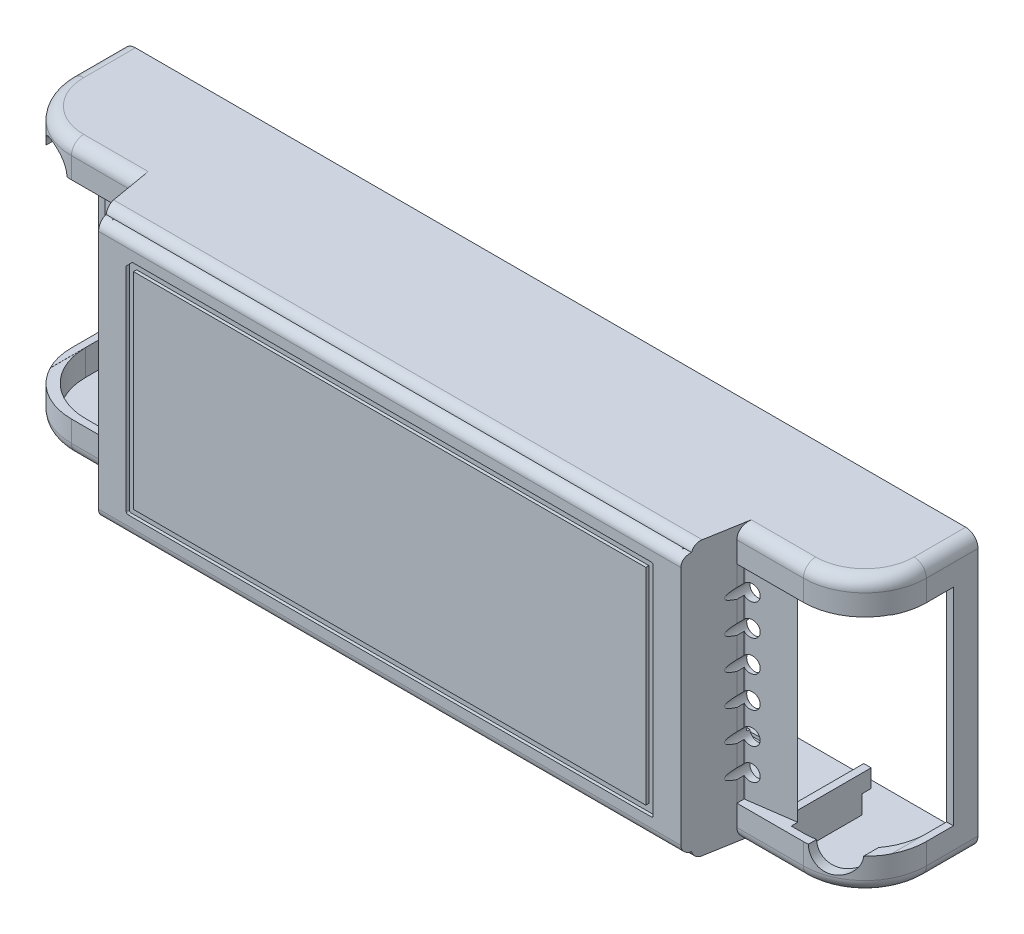
SolidWorks part; units mm, degrees
ref_plane "Front Plane" through (0, 0, 0) normal (0, 0, 1) x (1, 0, 0)
ref_plane "Top Plane" through (0, 0, 0) normal (0, 1, 0) x (1, 0, 0)
ref_plane "Right Plane" through (0, 0, 0) normal (1, 0, 0) x (0, 0, -1)
sketch "Sketch1" plane through (0, 0, 0) normal (0, 0, 1) x (1, 0, 0)
  line L1 (-34.7725, 22.265) -> (34.7725, 22.265)
  line L2 (-34.7725, 22.265) -> (-34.7725, -22.265)
  line L3 (-34.7725, -22.265) -> (34.7725, -22.265)
  line L4 (34.7725, 22.265) -> (34.7725, -22.265)
  line L5 (-34.7725, 22.265) -> (34.7725, -22.265) construction
  line L6 (-34.7725, -22.265) -> (34.7725, 22.265) construction
  point P0 (0, 0)
  dimension "D1" = 44.53
  dimension "D2" = 69.545
extrude "Boss-Extrude1" add sketch "Sketch1" along normal blind 26.17
sketch "Sketch2" plane through (0, 0, 26.17) normal (0, 0, 1) x (1, 0, 0)
  line L0 (-34.7725, -22.265) -> (34.7725, -22.265) construction
  line L1 (34.7725, 22.265) -> (13.9425, 22.265)
  line L2 (34.7725, 22.265) -> (34.7725, -22.265)
  line L3 (34.7725, -22.265) -> (13.9425, -22.265)
  line L4 (13.9425, 22.265) -> (13.9425, -22.265)
  dimension "D1" = 20.83
extrude "Cut-Extrude1" cut sketch "Sketch2" against normal blind 7.77
sketch "Sketch3" plane through (0, -22.265, 0) normal (0, -1, 0) x (1, 0, 0)
  line L0 (13.9425, 18.4) -> (13.9425, 26.17)
  line L1 (13.9425, 26.17) -> (12.5925, 26.17)
  line L2 (-34.7725, 26.17) -> (13.9425, 26.17) construction
  line L3 (12.5925, 26.17) -> (13.9425, 18.4)
  dimension "D1" = 22.18
extrude "Cut-Extrude2" cut sketch "Sketch3" against normal through all
sketch "Sketch4" plane through (0, 0, 18.4) normal (0, 0, 1) x (1, 0, 0)
  line L0 (13.9425, 22.265) -> (13.9425, -22.265) construction
  line L1 (63.8796, 16.865) -> (13.9425, 16.865)
  line L2 (63.8796, 16.865) -> (63.8796, -16.835)
  line L3 (63.8796, -16.835) -> (13.9425, -16.835)
  line L4 (13.9425, 16.865) -> (13.9425, -16.835)
  line L5 (34.7725, 22.265) -> (13.9425, 22.265) construction
  dimension "D1" = 33.7
  dimension "D2" = 0
  dimension "D3" = 5.4
extrude "Cut-Extrude3" cut sketch "Sketch4" against normal blind 1.2
sketch "Sketch5" plane through (0, 0, 18.4) normal (0, 0, 1) x (1, 0, 0)
  line L0 (13.9425, -16.835) -> (34.7725, -16.835) construction
  line L1 (33.6725, 16.865) -> (21.5925, 16.865)
  line L2 (33.6725, 16.865) -> (33.6725, -16.835)
  line L3 (33.6725, -16.835) -> (21.5925, -16.835)
  line L4 (21.5925, 16.865) -> (21.5925, -16.835)
  line L5 (34.7725, -22.265) -> (34.7725, -16.835) construction
  dimension "D1" = 33.7
  dimension "D2" = 12.08
  dimension "D3" = 1.1
extrude "Cut-Extrude4" cut sketch "Sketch5" against normal through all
sketch "Sketch6" plane through (34.7725, 0, 0) normal (1, 0, 0) x (0, 0, -1)
  line L0 (0, -22.265) -> (0, 22.265) construction
  line L1 (-10.22, -16.815) -> (-4, -16.815)
  line L2 (-10.22, -16.815) -> (-10.22, 16.815)
  line L3 (-10.22, 16.815) -> (-4, 16.815)
  line L4 (-4, -16.815) -> (-4, 16.815)
  line L5 (-18.4, 22.265) -> (0, 22.265) construction
  line L6 (-18.4, -22.265) -> (0, -22.265) construction
  dimension "D1" = 4
  dimension "D2" = 6.22
  dimension "D3" = 5.45
  dimension "D4" = 5.45
extrude "Cut-Extrude5" cut sketch "Sketch6" against normal blind 1.2
sketch "Sketch8" plane through (34.7725, 0, 0) normal (1, 0, 0) x (0, 0, -1)
  line L0 (-18.4, -22.265) -> (-18.4, -16.835) construction
  line L1 (-10.22, -16.815) -> (-18.4, -16.815)
  line L2 (-10.22, -16.815) -> (-10.22, 16.815)
  line L3 (-10.22, 16.815) -> (-18.4, 16.815)
  line L4 (-18.4, -16.815) -> (-18.4, 16.815)
extrude "Cut-Extrude6" cut sketch "Sketch8" against normal blind 1.2
sketch "Sketch9" plane through (21.5925, 0, 0) normal (1, 0, 0) x (0, 0, -1)
  line L0 (0, 16.865) -> (-17.2, 16.865) construction
  line L1 (0, -16.835) -> (-4.2, -16.835)
  line L2 (0, -16.835) -> (0, 16.865)
  line L3 (0, 16.865) -> (-4.2, 16.865)
  line L4 (-4.2, -16.835) -> (-4.2, 16.865)
  dimension "D1" = 4.2
extrude "Cut-Extrude7" cut sketch "Sketch9" against normal blind 5
sketch "Sketch11" plane through (21.5925, 0, 0) normal (1, 0, 0) x (0, 0, -1)
  line L0 (-4.2, 16.865) -> (-4.2, -16.835) construction
  line L1 (-16, -7.785) -> (-4.2, -7.785)
  line L2 (-16, -7.785) -> (-16, 7.815)
  line L3 (-16, 7.815) -> (-4.2, 7.815)
  line L4 (-4.2, -7.785) -> (-4.2, 7.815)
  line L5 (-17.2, -16.835) -> (-17.2, 16.865) construction
  line L6 (-4.2, -16.835) -> (-17.2, -16.835) construction
  dimension "D1" = 15.6
  dimension "D2" = 1.2
  dimension "D3" = 9.05
extrude "Cut-Extrude8" cut sketch "Sketch11" against normal blind 5
sketch "Sketch13" plane through (0, 16.865, 0) normal (0, -1, 0) x (1, 0, 0)
  line L0 (33.6725, 17.2) -> (21.5925, 17.2)
  line L1 (21.5925, 4.2) -> (21.5925, 17.2) construction
  line L2 (21.5925, 17.2) -> (21.5925, 4.2)
  line L3 (21.5925, 4.2) -> (16.5925, 4.2)
  line L4 (16.5925, 0) -> (16.5925, 4.2) construction
  line L5 (16.5925, 4.2) -> (21.5925, 4.2) construction
  line L6 (16.5925, 4.2) -> (16.5925, 0)
  line L7 (16.5925, 0) -> (33.6725, 0)
  line L8 (33.6725, 0) -> (33.6725, 17.2)
extrude "Cut-Extrude9" cut sketch "Sketch13" against normal blind 4.2
sketch "Sketch14" plane through (0, -16.835, 0) normal (0, 1, 0) x (1, 0, 0)
  line L0 (33.6725, -17.2) -> (21.5925, -17.2)
  line L1 (21.5925, -17.2) -> (21.5925, -4.2)
  line L2 (21.5925, -4.2) -> (16.5925, -4.2)
  line L3 (16.5925, -4.2) -> (16.5925, 0)
  line L4 (16.5925, 0) -> (33.6725, 0)
  line L5 (33.6725, 0) -> (33.6725, -17.2)
extrude "Cut-Extrude10" cut sketch "Sketch14" against normal blind 4.2
shell "Shell3" thickness 1.2
sketch "Sketch15" plane through (-34.7725, 0, 0) normal (-1, 0, 0) x (0, 0, 1)
  line L0 (26.17, 22.265) -> (0, 22.265) construction
  line L1 (24.97, 21.065) -> (0, 21.065)
  line L2 (24.97, 21.065) -> (24.97, -21.065)
  line L3 (24.97, -21.065) -> (0, -21.065)
  line L4 (0, 21.065) -> (0, -21.065)
  line L5 (26.17, 22.265) -> (26.17, -22.265) construction
  dimension "D1" = 1.2
  dimension "D2" = 1.2
extrude "Cut-Extrude11" cut sketch "Sketch15" against normal blind 4.2
sketch "Sketch16" plane through (16.5925, 0, 0) normal (1, 0, 0) x (0, 0, -1)
  line L0 (-16, -7.785) -> (-4.2, -7.785)
  line L1 (-4.2, -7.785) -> (-4.2, -21.035)
  line L2 (-4.2, -21.035) -> (0, -21.035)
  line L3 (0, -21.035) -> (0, 21.065)
  line L4 (0, 21.065) -> (-4.2, 21.065)
  line L5 (-4.2, 21.065) -> (-4.2, 7.815)
  line L6 (-4.2, 7.815) -> (-16, 7.815)
  line L7 (-16, 7.815) -> (-16, -7.785)
extrude "Cut-Extrude12" cut sketch "Sketch16" against normal blind 4.2
sketch "Sketch18" plane through (0, 0, 4.2) normal (0, 0, -1) x (-1, 0, 0)
  line L0 (-21.5925, 21.065) -> (-15.3925, 21.065) construction
  line L1 (-20.3925, 21.065) -> (-15.3925, 21.065)
  line L2 (-20.3925, 21.065) -> (-20.3925, 9.015)
  line L3 (-20.3925, 9.015) -> (-15.3925, 9.015)
  line L4 (-15.3925, 21.065) -> (-15.3925, 9.015)
  line L5 (-15.3925, 21.065) -> (-15.3925, 7.815) construction
  line L6 (-33.6725, -21.035) -> (-15.3925, -21.035) construction
  line L7 (-20.3925, -21.035) -> (-15.3925, -21.035)
  line L8 (-20.3925, -21.035) -> (-20.3925, -8.985)
  line L9 (-20.3925, -8.985) -> (-15.3925, -8.985)
  line L10 (-15.3925, -21.035) -> (-15.3925, -8.985)
  line L11 (-15.3925, -7.785) -> (-15.3925, -21.035) construction
  line L12 (-15.3925, -7.785) -> (-21.5925, -7.785) construction
  line L13 (-15.3925, 7.815) -> (-21.5925, 7.815) construction
  line L14 (-21.5925, -7.785) -> (-21.5925, -21.035) construction
  line L15 (-21.5925, 21.065) -> (-21.5925, 16.865) construction
  dimension "D1" = 1.2
  dimension "D2" = 1.2
  dimension "D3" = 1.2
  dimension "D4" = 1.2
extrude "Cut-Extrude13" cut sketch "Sketch18" against normal blind 4.2
sketch "Sketch19" plane through (0, 0, 24.97) normal (0, 0, -1) x (-1, 0, 0)
  line L0 (-11.583, 21.065) -> (-11.583, -21.065) construction
  line L1 (34.7725, -21.065) -> (-11.583, -21.065)
  line L2 (34.7725, -21.065) -> (34.7725, -19.565)
  line L3 (34.7725, -19.565) -> (-11.583, -19.565)
  line L4 (-11.583, -21.065) -> (-11.583, -19.565)
  line L5 (34.7725, -21.065) -> (34.7725, 21.065) construction
  line L6 (-11.583, 21.065) -> (34.7725, 21.065)
  line L7 (-11.583, 21.065) -> (-11.583, 19.565)
  line L8 (-11.583, 19.565) -> (34.7725, 19.565)
  line L9 (34.7725, 21.065) -> (34.7725, 19.565)
  dimension "D1" = 1.5
  dimension "D2" = 1.5
extrude "Boss-Extrude2" add sketch "Sketch19" along normal blind 2.5
sketch "Sketch22" plane through (0, 0, 26.17) normal (0, 0, 1) x (1, 0, 0)
  line L1 (12.5925, -22.265) -> (-37.0858, -22.265)
  line L2 (12.5925, -22.265) -> (12.5925, -21.065)
  line L3 (12.5925, -21.065) -> (-37.0858, -21.065)
  line L4 (-37.0858, -22.265) -> (-37.0858, -21.065)
  dimension "D1" = 1.2
extrude "Cut-Extrude16" cut sketch "Sketch22" against normal blind 1.5
sketch "Sketch23" plane through (12.5925, 0, 0) normal (-1, 0, 0) x (0, 0, 1)
  line L1 (24.67, -21.065) -> (26.17, -21.065)
  line L2 (24.67, -21.065) -> (24.67, -22.265)
  line L3 (24.67, -22.265) -> (26.17, -22.265)
  line L4 (26.17, -21.065) -> (26.17, -22.265)
extrude "Cut-Extrude17" cut sketch "Sketch23" against normal blind 1.5
sketch "Sketch24" plane through (0, 0, 26.17) normal (0, 0, 1) x (1, 0, 0)
  line L0 (12.5925, 22.265) -> (12.5925, -21.065) construction
  line L1 (-34.7725, 22.265) -> (12.5925, 22.265)
  line L2 (-34.7725, 22.265) -> (-34.7725, 21.065)
  line L3 (-34.7725, 21.065) -> (12.5925, 21.065)
  line L4 (12.5925, 22.265) -> (12.5925, 21.065)
  dimension "D1" = 1.2
extrude "Cut-Extrude18" cut sketch "Sketch24" against normal blind 1.5
sketch "Sketch25" plane through (12.5925, 0, 0) normal (-1, 0, 0) x (0, 0, 1)
  line L1 (24.67, 22.265) -> (26.17, 22.265)
  line L2 (24.67, 22.265) -> (24.67, 21.065)
  line L3 (24.67, 21.065) -> (26.17, 21.065)
  line L4 (26.17, 22.265) -> (26.17, 21.065)
extrude "Cut-Extrude19" cut sketch "Sketch25" against normal blind 1.5
sketch "Sketch26" plane through (0, 0, 26.17) normal (0, 0, 1) x (1, 0, 0)
  line L0 (-34.7725, 21.065) -> (11.583, 21.065) construction
  line L1 (8.0925, 17.9519) -> (-34.7725, 17.9519)
  line L2 (8.0925, 17.9519) -> (8.0925, -17.955)
  line L3 (8.0925, -17.955) -> (-34.7725, -17.955)
  line L4 (-34.7725, 17.9519) -> (-34.7725, -17.955)
  line L5 (12.5925, 21.065) -> (12.5925, -21.065) construction
  line L6 (-34.7725, 21.065) -> (-34.7725, -21.065) construction
  line L7 (12.5925, -21.065) -> (-34.7725, -21.065) construction
  line L9 (-34.7725, 16.7519) -> (6.8925, 16.7519)
  line L10 (-34.7725, 16.7519) -> (-34.7725, -16.755)
  line L11 (-34.7725, -16.755) -> (6.8925, -16.755)
  line L12 (6.8925, 16.7519) -> (6.8925, -16.755)
  line M9 (-34.7725, 21.065) -> (-34.7725, -21.065)
  dimension "D1" = 3.1131
  dimension "D2" = 4.5
  dimension "D3" = 0
  dimension "D4" = 3.11
  dimension "D5" = 1.2
  dimension "D6" = 1.2
  dimension "D7" = 1.2
extrude "Cut-Extrude20" cut sketch "Sketch26" against normal blind 0.5 contours L9 L12 L11 L3 L2 L1 M9
fillet "Fillet1" radius 1.5 4 edges at (-11.09, 21.065, 26.17) (-10.9597, 22.265, 24.67) (-11.09, -21.065, 26.17) (-10.9597, -22.265, 24.67)
fillet "Fillet5" radius 10 2 edges at (33.6725, 18.965, 17.2) (33.6725, -18.935, 17.2)
fillet "Fillet6" radius 10 2 edges at (34.7725, -19.55, 18.4) (34.7725, 19.565, 18.4)
fillet "Fillet7" radius 2 6 edges at (19.3575, 22.265, 18.4) (31.8436, 22.265, 15.4711) (19.3575, -22.265, 18.4) (31.8436, -22.265, 15.4711) (34.7725, 22.265, 4.2) (34.7725, -22.265, 4.2)
mirror "Mirror1" about plane through (-34.7725, 22.265, 26.17) normal (1, 0, 0) of bodies 122
sketch "Sketch27" plane through (0, 0, 4.2) normal (0, 0, -1) x (-1, 0, 0)
  line L1 (89.9375, 9.015) -> (84.9375, 9.015) construction
  line L2 (84.9375, 7.815) -> (87.8509, 7.815)
  line L3 (84.9375, 7.815) -> (84.9375, 9.015)
  line L4 (84.9375, 9.015) -> (87.8509, 9.015)
  line L5 (87.8509, 7.815) -> (87.8509, 9.015)
  line L6 (84.9375, -7.785) -> (91.1375, -7.785) construction
  line L7 (84.9375, -8.985) -> (87.8509, -8.985)
  line L8 (84.9375, -8.985) -> (84.9375, -7.785)
  line L9 (84.9375, -7.785) -> (87.8509, -7.785)
  line L10 (87.8509, -8.985) -> (87.8509, -7.785)
extrude "Cut-Extrude21" cut sketch "Sketch27" against normal up to surface (11.8 mm away) up to face at (-87.1958, 0.015, 16)
sketch "Sketch28" plane through (0, 0, 4.2) normal (0, 0, -1) x (-1, 0, 0)
  line L0 (-15.3925, -8.985) -> (-20.3925, -8.985) construction
  line L1 (-15.3925, -7.785) -> (-18.0902, -7.785)
  line L2 (-15.3925, -7.785) -> (-15.3925, -8.985)
  line L3 (-15.3925, -8.985) -> (-18.0902, -8.985)
  line L4 (-18.0902, -7.785) -> (-18.0902, -8.985)
  line L5 (-15.3925, 7.815) -> (-21.5925, 7.815) construction
  line L6 (-15.3925, 9.015) -> (-18.0902, 9.015)
  line L7 (-15.3925, 9.015) -> (-15.3925, 7.815)
  line L8 (-15.3925, 7.815) -> (-18.0902, 7.815)
  line L9 (-18.0902, 9.015) -> (-18.0902, 7.815)
extrude "Cut-Extrude22" cut sketch "Sketch28" against normal up to surface (11.8 mm away) up to face at (17.6508, 0.015, 16)
sketch "Sketch29" plane through (0, 0, 16) normal (0, 0, -1) x (-1, 0, 0)
  line L0 (-12.7425, 18.065) -> (-12.7425, -18.035) construction
  line L1 (-18.0902, -7.785) -> (-12.7425, -7.785)
  line L2 (-18.0902, -7.785) -> (-18.0902, 7.8605)
  line L3 (-18.0902, 7.8605) -> (-12.7425, 7.8605)
  line L4 (-12.7425, -7.785) -> (-12.7425, 7.8605)
extrude "Cut-Extrude23" cut sketch "Sketch29" against normal blind 0.5
sketch "Sketch30" plane through (0, 0, 16.5) normal (0, 0, -1) x (-1, 0, 0)
  line L0 (-13.9425, 16.865) -> (-13.9425, -16.835) construction
  line L1 (-13.9425, -16.835) -> (-24.7725, -16.835) construction
  line L6 (-13.9425, 16.865) -> (-13.9425, -16.835) construction
  circle A0 centre (-14.9425, -2.525) radius 1.3
  circle A1 centre (-14.9425, -12.685) radius 1.3
  circle A3 centre (-14.9425, -7.605) radius 1.3
  circle A5 centre (-14.9425, 7.635) radius 1.3
  circle A6 centre (-14.9425, 12.715) radius 1.3
  circle A7 centre (-14.9425, 2.555) radius 1.3
  dimension "D1" = 2.6
  dimension "D2" = 1
  dimension "D3" = 1
  dimension "D7" = 1
  dimension "D8" = 5.08
  dimension "D9" = 5.08
  dimension "D4" = 1
  dimension "D5" = 1
  dimension "D6" = 1
  dimension "D10" = 5.08
  dimension "D11" = 5.08
  dimension "D12" = 5.08
  dimension "D13" = 4.15
extrude "Cut-Extrude24" cut sketch "Sketch30" along normal through all both and the other way through all
sketch "Sketch31" plane through (0, 0, 16) normal (0, 0, -1) x (-1, 0, 0)
  line L0 (82.2875, 18.065) -> (82.2875, -18.035) construction
  line L1 (87.8509, -7.785) -> (82.2875, -7.785)
  line L2 (87.8509, -7.785) -> (87.8509, 7.8686)
  line L3 (87.8509, 7.8686) -> (82.2875, 7.8686)
  line L4 (82.2875, -7.785) -> (82.2875, 7.8686)
extrude "Cut-Extrude25" cut sketch "Sketch31" against normal blind 0.5
sketch "Sketch32" plane through (0, 0, 16.5) normal (0, 0, -1) x (-1, 0, 0)
  line L1 (87.8509, 7.8686) -> (82.2875, 7.8686) construction
  circle A0 centre (84.4387, -5.4114) radius 1.5
  circle A1 centre (84.4383, 4.7486) radius 1.5
  dimension "D1" = 3
  dimension "D2" = 3
  dimension "D3" = 10.16
  dimension "D4" = 3.12
extrude "Cut-Extrude26" cut sketch "Sketch32" against normal through all
chamfer "Chamfer2" distance 1 angle 45 1 edges at (-77.6375, 17.9519, 25.92)
fillet "Fillet8" radius 0.3 3 edges at (-77.6375, -17.955, 25.92) (8.0925, -17.955, 25.92) (8.0925, 17.9519, 25.92)
sketch "Sketch33" plane through (0, 0, 18.4) normal (0, 0, 1) x (1, 0, 0)
  line L0 (-103.2175, 16.865) -> (-94.3175, 16.865) construction
  line L1 (-83.4875, 20.265) -> (-83.4875, 16.865) construction
  circle A0 centre (-98.1775, 16.865) radius 3.09
  dimension "D1" = 6.18
  dimension "D2" = 14.69
extrude "Cut-Extrude27" cut sketch "Sketch33" against normal through all
sketch "Sketch34" plane through (0, 0, 18.4) normal (0, 0, 1) x (1, 0, 0)
  line L0 (33.6725, -16.835) -> (24.7725, -16.835) construction
  line L1 (13.9425, -16.835) -> (13.9425, -20.265) construction
  circle A0 centre (28.6325, -16.835) radius 3.09
  dimension "D2" = 6.18
  dimension "D1" = 14.69
extrude "Cut-Extrude28" cut sketch "Sketch34" against normal through all
chamfer "Chamfer5" distance 7.5 angle 8 1 edges at (21.5925, 0.015, 17.2)
chamfer "Chamfer6" distance 7.5 angle 8 1 edges at (-91.1375, 0.015, 17.2)
sketch "Sketch35" plane through (0, 21.065, 0) normal (0, -1, 0) x (1, 0, 0)
  line L0 (-103.2175, 0) -> (33.6725, 0) construction
  line L1 (5.1925, 3) -> (-1.3075, 3)
  line L2 (5.1925, 3) -> (5.1925, 5)
  line L3 (5.1925, 5) -> (-1.3075, 5)
  line L4 (-1.3075, 3) -> (-1.3075, 5)
  line L5 (33.6725, 0) -> (33.6725, 7.2) construction
  line L6 (-103.2175, 0) -> (-103.2175, 7.2) construction
  line L7 (-74.8575, 5) -> (-68.3575, 5)
  line L8 (-74.8575, 5) -> (-74.8575, 3)
  line L9 (-74.8575, 3) -> (-68.3575, 3)
  line L10 (-68.3575, 5) -> (-68.3575, 3)
  dimension "D1" = 6.5
  dimension "D2" = 3
  dimension "D3" = 2
  dimension "D4" = 28.48
  dimension "D5" = 6.5
  dimension "D6" = 2
  dimension "D7" = 28.36
extrude "Cut-Extrude29" cut sketch "Sketch35" against normal blind 0.5
chamfer "Chamfer7" distance 0.5 angle 45 2 edges at (-71.6075, 21.065, 5) (1.9425, 21.065, 5)
mirror "Mirror4" about plane through (0, 0, 0) normal (0, 1, 0) of "Cut-Extrude29"
chamfer "Chamfer8" distance 0.5 angle 45 2 edges at (-71.6075, -21.065, 5) (1.9425, -21.065, 5)
sketch "Sketch36" plane through (0, 0, 4.2) normal (0, 0, -1) x (-1, 0, 0)
  line L0 (-20.3925, 21.065) -> (-20.3925, 9.015) construction
  line L1 (-21.5925, 21.065) -> (-20.3925, 21.065)
  line L2 (-21.5925, 21.065) -> (-21.5925, 18.075)
  line L3 (-21.5925, 18.075) -> (-20.3925, 18.075)
  line L4 (-20.3925, 21.065) -> (-20.3925, 18.075)
  line L5 (-21.5925, -7.785) -> (-21.5925, -21.035) construction
  line L6 (-20.3925, -21.035) -> (-21.5925, -21.035)
  line L7 (-20.3925, -21.035) -> (-20.3925, -18.0418)
  line L8 (-20.3925, -18.0418) -> (-21.5925, -18.0418)
  line L9 (-21.5925, -21.035) -> (-21.5925, -18.0418)
  line L10 (91.1375, 21.065) -> (91.1375, 7.815) construction
  line L19 (89.9375, 21.065) -> (91.1375, 21.065)
  line L20 (89.9375, 21.065) -> (89.9375, 18.065)
  line L21 (89.9375, 18.065) -> (91.1375, 18.065)
  line L22 (91.1375, 21.065) -> (91.1375, 18.065)
  line L24 (89.9375, -18.035) -> (91.1375, -18.035)
  line L25 (89.9375, -18.035) -> (89.9375, -21.035)
  line L26 (89.9375, -21.035) -> (91.1375, -21.035)
  line L27 (91.1375, -18.035) -> (91.1375, -21.035)
  dimension "D1" = 2.9932
  dimension "D2" = 2.99
extrude "Cut-Extrude31" cut sketch "Sketch36" against normal blind 1.5
sketch "Sketch37" plane through (21.5925, 0, 0) normal (1, 0, 0) x (0, 0, -1)
  line L2 (-16.1459, -15.1284) -> (-16.1459, 15.665)
  line L3 (-16.1459, 15.665) -> (-4.2, 15.665)
  line L4 (-4.2, -15.1284) -> (-4.2, 15.665)
  line L5 (-4.2, 18.075) -> (-4.2, 7.815) construction
  line L6 (-16.1459, -15.1284) -> (-4.2, -15.1284)
extrude "Cut-Extrude32" cut sketch "Sketch37" against normal up to surface (3.5023 mm away) up to face at (18.0902, -8.385, 10.1)
